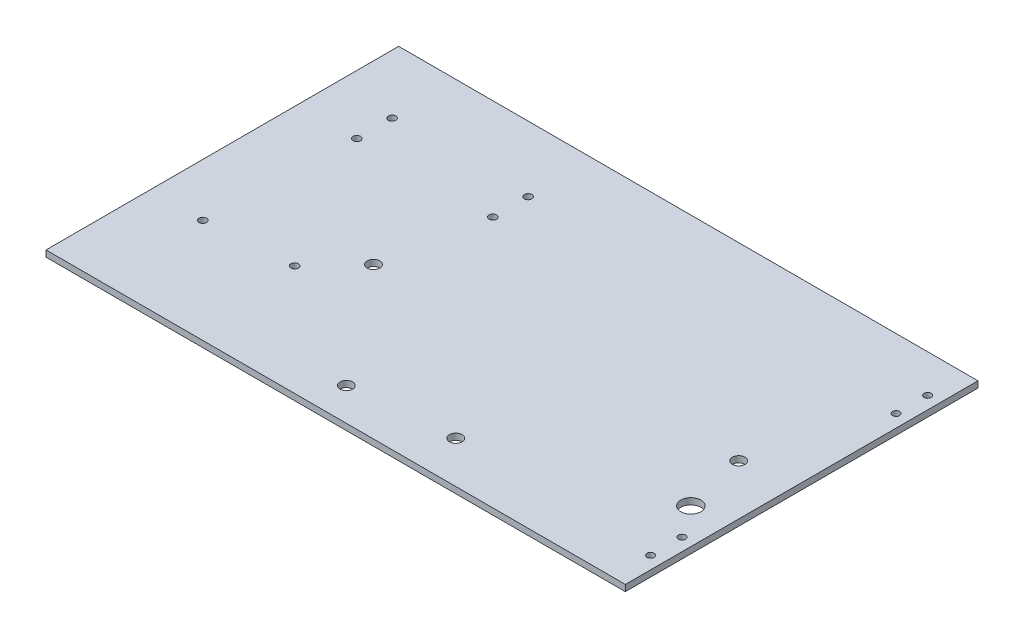
SolidWorks part; units mm, degrees
ref_plane "Front Plane" through (0, 0, 0) normal (0, 0, 1) x (1, 0, 0)
ref_plane "Top Plane" through (0, 0, 0) normal (0, 1, 0) x (1, 0, 0)
ref_plane "Right Plane" through (0, 0, 0) normal (1, 0, 0) x (0, 0, -1)
sketch "Sketch1" plane through (0, 0, 0) normal (0, 1, 0) x (1, 0, 0)
  line L1 (-158.75, 88.9) -> (158.75, 88.9)
  line L2 (-158.75, 88.9) -> (-158.75, -88.9)
  line L3 (-158.75, -88.9) -> (158.75, -88.9)
  line L4 (158.75, 88.9) -> (158.75, -88.9)
  line L5 (-158.75, 88.9) -> (158.75, -88.9) construction
  line L6 (-158.75, -88.9) -> (158.75, 88.9) construction
  circle A0 centre (-69.85, -12.7) radius 3.175
  circle A1 centre (107.95, -6.35) radius 3.175
  circle A4 centre (-129.032, 55.88) radius 1.905
  circle A5 centre (-60.452, 55.88) radius 1.905
  circle A7 centre (-129.032, 38.1) radius 1.905
  circle A8 centre (-60.452, 38.1) radius 1.905
  point P0 (0, 0)
  dimension "D3" = 6.35
  dimension "D4" = 6.35
  dimension "D14" = 3.81
  dimension "D17" = 17.78
  dimension "D1" = 317.5
  dimension "D2" = 177.8
  dimension "D5" = 88.9
  dimension "D6" = 266.7
  dimension "D7" = 95.25
  dimension "D8" = 76.2
  dimension "D13" = 29.718
  dimension "D15" = 68.58
  dimension "D16" = 127
extrude "Boss-Extrude1" add sketch "Sketch1" along normal blind 3.175
sketch "Sketch2" plane through (0, 3.175, 0) normal (0, 1, 0) x (1, 0, 0)
  line L0 (-158.75, 88.9) -> (-158.75, -88.9) construction
  line L1 (-158.75, -88.9) -> (158.75, -88.9) construction
  circle A0 centre (-89.0817, -33.177) radius 1.905
  circle A1 centre (-132.1376, -36.4483) radius 1.905
  dimension "D1" = 3.81
  dimension "D2" = 69.6683
  dimension "D3" = 52.4517
  dimension "D4" = 55.723
  dimension "D5" = 43.18
extrude "Cut-Extrude1" cut sketch "Sketch2" against normal through all
sketch "Sketch3" plane through (0, 0, 0) normal (0, -1, 0) x (-1, 0, 0)
  line L0 (158.75, -88.9) -> (-158.75, -88.9) construction
  line L1 (158.75, 88.9) -> (158.75, -88.9) construction
  circle A0 centre (23.8295, -72.39) radius 3.175
  circle A1 centre (-26.7643, -67.818) radius 3.175
  dimension "D1" = 6.35
  dimension "D2" = 4.572
  dimension "D3" = 16.51
  dimension "D4" = 185.5143
  dimension "D5" = 50.8
extrude "Cut-Extrude2" cut sketch "Sketch3" against normal through all
sketch "Sketch4" plane through (0, 3.175, 0) normal (0, 1, 0) x (1, 0, 0)
  line L0 (-158.75, -88.9) -> (158.75, -88.9) construction
  line L1 (158.75, 88.9) -> (133.35, 88.9)
  line L2 (158.75, 88.9) -> (158.75, -88.9)
  line L3 (158.75, -88.9) -> (133.35, -88.9)
  line L4 (133.35, 88.9) -> (133.35, -88.9)
  dimension "D1" = 25.4
extrude "Cut-Extrude3" cut sketch "Sketch4" against normal through all
sketch "Sketch5" plane through (0, 3.175, 0) normal (0, 1, 0) x (1, 0, 0)
  line L0 (133.35, 88.9) -> (-158.75, 88.9) construction
  line L1 (133.35, 88.9) -> (133.35, -88.9) construction
  circle A0 centre (115.57, -38.1) radius 5.08
  dimension "D3" = 10.16
  dimension "D1" = 127
  dimension "D2" = 17.78
extrude "Cut-Extrude4" cut sketch "Sketch5" against normal through all
sketch "Sketch6" plane through (0, 0, 0) normal (0, -1, 0) x (1, 0, 0)
  line L0 (-158.75, 88.9) -> (133.35, 88.9) construction
  line L1 (133.35, -88.9) -> (133.35, 88.9) construction
  line L2 (133.35, -88.9) -> (-158.75, -88.9) construction
  circle A0 centre (127, 69.85) radius 1.8034
  circle A2 centre (127, 53.975) radius 1.8034
  circle A3 centre (127, -53.975) radius 1.8034
  circle A4 centre (127, -69.85) radius 1.8034
  point P12 (0, 0)
  dimension "D4" = 3.6068
  dimension "D5" = 6.35
  dimension "D1" = 15.875
  dimension "D2" = 19.05
  dimension "D3" = 6.35
  dimension "D6" = 15.875
  dimension "D7" = 19.05
extrude "Cut-Extrude5" cut sketch "Sketch6" against normal through all
